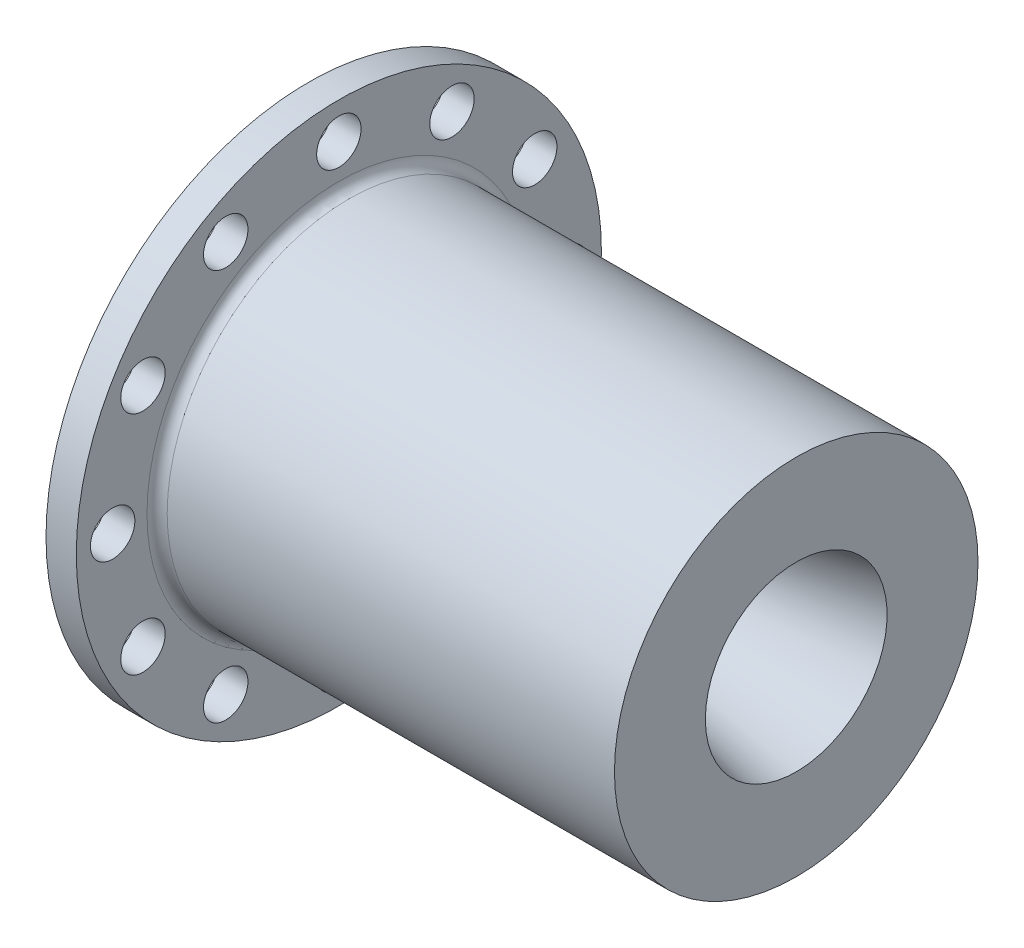
SolidWorks part; units mm, degrees
ref_plane "Front Plane" through (0, 0, 0) normal (0, 0, 1) x (1, 0, 0)
ref_plane "Top Plane" through (0, 0, 0) normal (0, 1, 0) x (1, 0, 0)
ref_plane "Right Plane" through (0, 0, 0) normal (1, 0, 0) x (0, 0, -1)
sketch "Chamber Revolve" plane through (0, 0, 0) normal (0, 0, 1) x (1, 0, 0)
  line L0 (3.81, 22.86) -> (61.3318, 22.86)
  line L1 (61.3318, 22.86) -> (61.3318, 11.43)
  line L2 (61.3318, 11.43) -> (43.198, 7.5756)
  line L3 (43.198, 7.5756) -> (41.674, 7.5756)
  line L4 (41.674, 7.5756) -> (38.1, 15.24)
  line L5 (38.1, 15.24) -> (0, 15.24)
  line L6 (0, 15.24) -> (0, 18.415)
  line L7 (0, 18.415) -> (1.016, 18.415)
  line L8 (1.016, 18.415) -> (1.016, 20.955)
  line L9 (1.016, 20.955) -> (0, 20.955)
  line L10 (0, 20.955) -> (0, 33.02)
  line L11 (0, 33.02) -> (3.81, 33.02)
  line L12 (3.81, 33.02) -> (3.81, 22.86)
  line L13 (0, 0) -> (66.3921, 0) construction
  point P15 (0, 0)
  point P16 (48.7693, 7.5756)
  point P18 (43.9865, 7.5756)
  point P19 (0, 16.7019)
  point P20 (4.361, 29.0526)
  dimension "D1" = 15.1511
  dimension "D2" = 30.48
  dimension "D3" = 22.86
  dimension "D5" = 38.1
  dimension "D6" = 65
  dimension "D8" = 1.524
  dimension "D9" = 3.175
  dimension "D10" = 1.016
  dimension "D11" = 2.54
  dimension "D12" = 10.16
  dimension "D13" = 3.81
revolve "Revolve1" add sketch "Chamber Revolve" angle 360 about L13
fillet "Fillet1" radius 1.27 1 edges at (3.81, 0, 22.86)
sketch "Sketch2" plane through (0, 0, 0) normal (-1, 0, 0) x (0, 0, 1)
  line L0 (0, 0) -> (0, 33.02) construction
  circle A0 centre (0, 28.448) radius 2.794
  circle A1 centre (0, 0) radius 33.02 construction
  point P8 (0, 27.94)
  dimension "D2" = 5.588
  dimension "D1" = 4.572
extrude "Cut-Extrude1" cut sketch "Sketch2" against normal up to next
pattern_circular "CirPattern1" count 12 over 360 about axis through (0, 0, 0) along (-1, 0, 0) of "Cut-Extrude1"
equation "\"Throat Diameter\"= 0.5965"
equation "\"D1@Chamber Revolve\"=\"Throat Diameter\""
equation "\"Exit Diameter\"= 0.90"
equation "\"D3@Chamber Revolve\"=\"Exit Diameter\""
